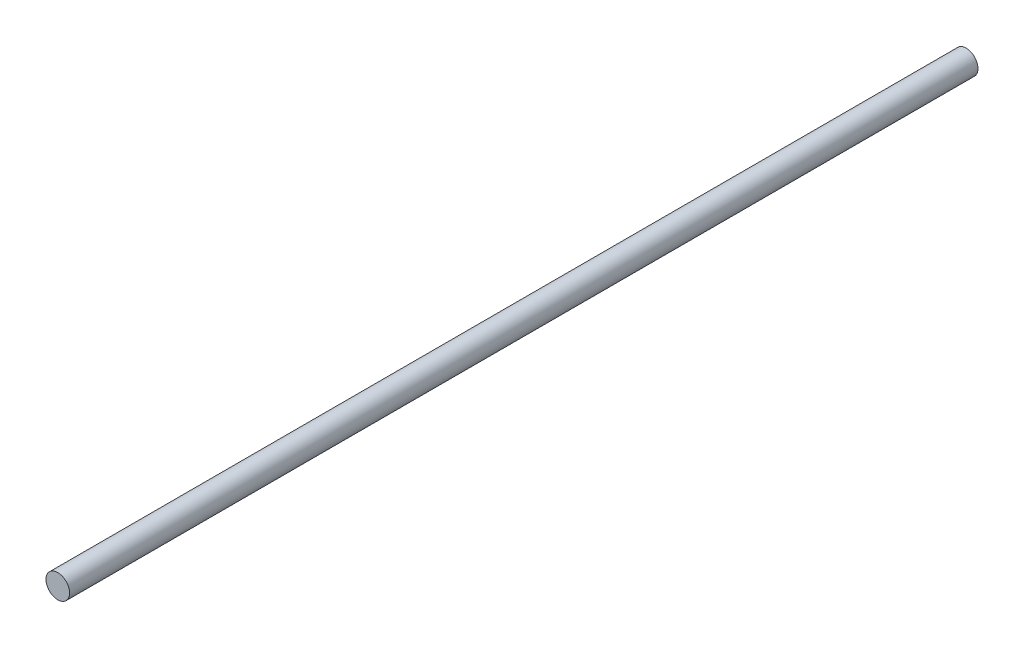
SolidWorks part; units mm, degrees
ref_plane "Front Plane" through (0, 0, 0) normal (0, 0, 1) x (1, 0, 0)
ref_plane "Top Plane" through (0, 0, 0) normal (0, 1, 0) x (1, 0, 0)
ref_plane "Right Plane" through (0, 0, 0) normal (1, 0, 0) x (0, 0, -1)
sketch "Sketch1" plane through (0, 0, 0) normal (0, 0, 1) x (1, 0, 0)
  circle A0 centre (0, 0) radius 4.953
  dimension "D1" = 9.906
extrude "Boss-Extrude1" add sketch "Sketch1" along normal blind 190.5 and the other way blind 190.5
